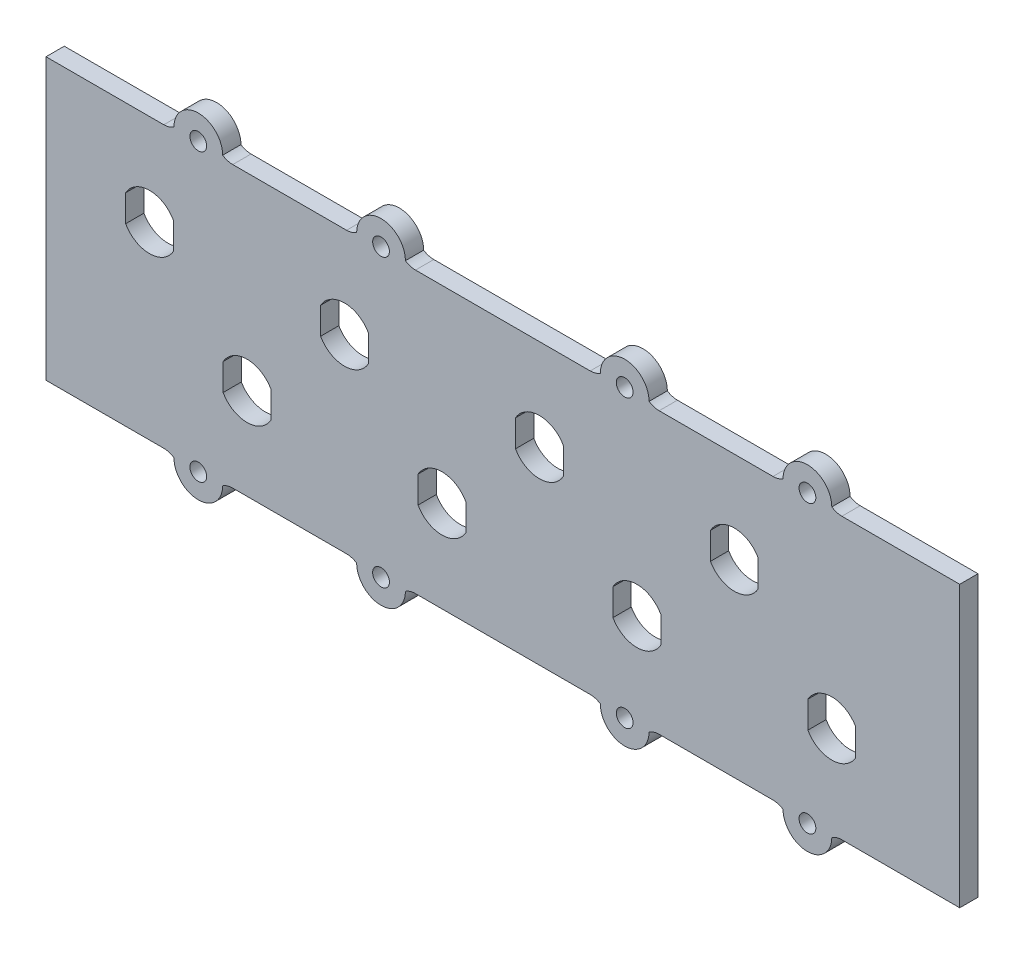
SolidWorks part; units mm, degrees
material "Aircraft Ply"
ref_plane "Front Plane" through (0, 0, 0) normal (0, 0, 1) x (1, 0, 0)
ref_plane "Top Plane" through (0, 0, 0) normal (0, 1, 0) x (1, 0, 0)
ref_plane "Right Plane" through (0, 0, 0) normal (1, 0, 0) x (0, 0, -1)
sketch "Sketch1" plane through (0, 0, 0) normal (0, 0, 1) x (1, 0, 0)
  line L0 (-75, 8) -> (75, 8) construction
  line L1 (-75, 0) -> (75, 0) construction
  line L8 (-75, 23) -> (-75, -23)
  line L9 (-44.3417, -23) -> (-25.6583, -23)
  line L10 (-14.3417, -23) -> (14.3417, -23)
  line L11 (25.6583, -23) -> (44.3417, -23)
  line L12 (75, -23) -> (75, 23)
  line L13 (44.3417, 23) -> (25.6583, 23)
  line L14 (14.3417, 23) -> (-14.3417, 23)
  line L15 (-25.6583, 23) -> (-44.3417, 23)
  line L16 (-75, 23) -> (-75, -23)
  line L17 (-44.3417, -23) -> (-25.6583, -23)
  line L18 (-14.3417, -23) -> (14.3417, -23)
  line L19 (25.6583, -23) -> (44.3417, -23)
  line L20 (75, -23) -> (75, 23)
  line L21 (44.3417, 23) -> (25.6583, 23)
  line L22 (14.3417, 23) -> (-14.3417, 23)
  line L23 (-25.6583, 23) -> (-44.3417, 23)
  line L30 (-75, -23) -> (-55.6583, -23)
  line L31 (-75, -23) -> (-55.6583, -23)
  line L32 (55.6583, -23) -> (75, -23)
  line L33 (55.6583, -23) -> (75, -23)
  line L34 (75, 23) -> (55.6583, 23)
  line L35 (75, 23) -> (55.6583, 23)
  line L36 (-55.6583, 23) -> (-75, 23)
  line L37 (-55.6583, 23) -> (-75, 23)
  line L38 (-54.075, 10.201) -> (-54.075, 5.799)
  line L39 (-61.925, 10.201) -> (-61.925, 5.799)
  line L40 (-29.925, 10.201) -> (-29.925, 5.799)
  line L41 (-22.075, 10.201) -> (-22.075, 5.799)
  line L42 (2.075, 10.201) -> (2.075, 5.799)
  line L43 (9.925, 10.201) -> (9.925, 5.799)
  line L44 (34.075, 10.201) -> (34.075, 5.799)
  line L45 (41.925, 10.201) -> (41.925, 5.799)
  line L46 (-13.925, -5.799) -> (-13.925, -10.201)
  line L47 (-6.075, -5.799) -> (-6.075, -10.201)
  line L48 (18.075, -5.799) -> (18.075, -10.201)
  line L49 (25.925, -5.799) -> (25.925, -10.201)
  line L50 (50.075, -5.799) -> (50.075, -10.201)
  line L51 (57.925, -5.799) -> (57.925, -10.201)
  line L52 (-45.925, -5.799) -> (-45.925, -10.201)
  line L53 (-38.075, -5.799) -> (-38.075, -10.201)
  circle A0 centre (-50, 23.5) radius 1.375 construction
  circle A1 centre (-20, 23.5) radius 1.375 construction
  circle A2 centre (20, 23.5) radius 1.375 construction
  circle A3 centre (50, 23.5) radius 1.375 construction
  circle A4 centre (50, -23.5) radius 1.375 construction
  circle A5 centre (20, -23.5) radius 1.375 construction
  circle A6 centre (-20, -23.5) radius 1.375 construction
  circle A7 centre (-50, -23.5) radius 1.375 construction
  circle A8 centre (-50, -23.5) radius 1.375
  circle A9 centre (-20, -23.5) radius 1.375
  circle A10 centre (20, -23.5) radius 1.375
  circle A11 centre (50, -23.5) radius 1.375
  circle A12 centre (50, 23.5) radius 1.375
  circle A13 centre (20, 23.5) radius 1.375
  circle A14 centre (-20, 23.5) radius 1.375
  circle A15 centre (-50, 23.5) radius 1.375
  circle A16 centre (-58, 8) radius 4.5
  circle A17 centre (-26, 8) radius 4.5
  circle A18 centre (6, 8) radius 4.5
  circle A19 centre (38, 8) radius 4.5
  circle A20 centre (-42, -8) radius 4.5
  circle A21 centre (-10, -8) radius 4.5
  circle A22 centre (22, -8) radius 4.5
  circle A23 centre (54, -8) radius 4.5
  arc A29 (-54, -23.5) -> (-55.6583, -23) centre (-55.6583, -26) ccw
  arc A30 (-54, -23.5) -> (-46, -23.5) centre (-50, -23.5) ccw
  arc A31 (-44.3417, -23) -> (-46, -23.5) centre (-44.3417, -26) ccw
  arc A32 (-24, -23.5) -> (-25.6583, -23) centre (-25.6583, -26) ccw
  arc A33 (-24, -23.5) -> (-16, -23.5) centre (-20, -23.5) ccw
  arc A34 (-14.3417, -23) -> (-16, -23.5) centre (-14.3417, -26) ccw
  arc A35 (16, -23.5) -> (14.3417, -23) centre (14.3417, -26) ccw
  arc A36 (16, -23.5) -> (24, -23.5) centre (20, -23.5) ccw
  arc A37 (25.6583, -23) -> (24, -23.5) centre (25.6583, -26) ccw
  arc A38 (46, -23.5) -> (44.3417, -23) centre (44.3417, -26) ccw
  arc A39 (46, -23.5) -> (54, -23.5) centre (50, -23.5) ccw
  arc A40 (55.6583, -23) -> (54, -23.5) centre (55.6583, -26) ccw
  arc A43 (54, 23.5) -> (55.6583, 23) centre (55.6583, 26) ccw
  arc A44 (54, 23.5) -> (46, 23.5) centre (50, 23.5) ccw
  arc A45 (44.3417, 23) -> (46, 23.5) centre (44.3417, 26) ccw
  arc A46 (24, 23.5) -> (25.6583, 23) centre (25.6583, 26) ccw
  arc A47 (24, 23.5) -> (16, 23.5) centre (20, 23.5) ccw
  arc A48 (14.3417, 23) -> (16, 23.5) centre (14.3417, 26) ccw
  arc A49 (-16, 23.5) -> (-14.3417, 23) centre (-14.3417, 26) ccw
  arc A50 (-16, 23.5) -> (-24, 23.5) centre (-20, 23.5) ccw
  arc A51 (-25.6583, 23) -> (-24, 23.5) centre (-25.6583, 26) ccw
  arc A52 (-46, 23.5) -> (-44.3417, 23) centre (-44.3417, 26) ccw
  arc A53 (-46, 23.5) -> (-54, 23.5) centre (-50, 23.5) ccw
  arc A54 (-55.6583, 23) -> (-54, 23.5) centre (-55.6583, 26) ccw
  arc A57 (-54, -23.5) -> (-55.6583, -23) centre (-55.6583, -26) ccw
  arc A58 (-54, -23.5) -> (-46, -23.5) centre (-50, -23.5) ccw
  arc A59 (-44.3417, -23) -> (-46, -23.5) centre (-44.3417, -26) ccw
  arc A60 (-24, -23.5) -> (-25.6583, -23) centre (-25.6583, -26) ccw
  arc A61 (-24, -23.5) -> (-16, -23.5) centre (-20, -23.5) ccw
  arc A62 (-14.3417, -23) -> (-16, -23.5) centre (-14.3417, -26) ccw
  arc A63 (16, -23.5) -> (14.3417, -23) centre (14.3417, -26) ccw
  arc A64 (16, -23.5) -> (24, -23.5) centre (20, -23.5) ccw
  arc A65 (25.6583, -23) -> (24, -23.5) centre (25.6583, -26) ccw
  arc A66 (46, -23.5) -> (44.3417, -23) centre (44.3417, -26) ccw
  arc A67 (46, -23.5) -> (54, -23.5) centre (50, -23.5) ccw
  arc A68 (55.6583, -23) -> (54, -23.5) centre (55.6583, -26) ccw
  arc A71 (54, 23.5) -> (55.6583, 23) centre (55.6583, 26) ccw
  arc A72 (54, 23.5) -> (46, 23.5) centre (50, 23.5) ccw
  arc A73 (44.3417, 23) -> (46, 23.5) centre (44.3417, 26) ccw
  arc A74 (24, 23.5) -> (25.6583, 23) centre (25.6583, 26) ccw
  arc A75 (24, 23.5) -> (16, 23.5) centre (20, 23.5) ccw
  arc A76 (14.3417, 23) -> (16, 23.5) centre (14.3417, 26) ccw
  arc A77 (-16, 23.5) -> (-14.3417, 23) centre (-14.3417, 26) ccw
  arc A78 (-16, 23.5) -> (-24, 23.5) centre (-20, 23.5) ccw
  arc A79 (-25.6583, 23) -> (-24, 23.5) centre (-25.6583, 26) ccw
  arc A80 (-46, 23.5) -> (-44.3417, 23) centre (-44.3417, 26) ccw
  arc A81 (-46, 23.5) -> (-54, 23.5) centre (-50, 23.5) ccw
  arc A82 (-55.6583, 23) -> (-54, 23.5) centre (-55.6583, 26) ccw
  dimension "D2" = 9
  dimension "D3" = 8
  dimension "D6" = 17
  dimension "D7" = 7.85
  dimension "D1" = 0
  dimension "D4" = 4
  dimension "D5" = 2
extrude "Boss-Extrude1" add sketch "Sketch1" along normal blind 3 contours A82 L37 L16 L31 A57 A58 A59 L17 A60 A61 A62 L18 A63 A64 A65 L19 A66 A67 A68 L33 L20 L35 A71 A72 A73 L21 A74 A75 A76 L22 A77 A78 A79 L23 A80 A81 A23 A22 A21 | L39 A16 | L38 A16 | L40 A17 | L41 A17 | L42 A18 | L43 A18 | L44 A19 | L45 A19 | L50 A23 | L51 A23 | L48 A22 | L49 A22 | L46 A21 | L47 A21 | L52 A20 | L53 A20 region at (0.1547, 0, 0) region at (-53.8437, 8, 0) region at (-62.1563, 8, 0) region at (-30.1563, 8, 0) region at (-21.8437, 8, 0) region at (1.8437, 8, 0) region at (10.1563, 8, 0) region at (33.8437, 8, 0) region at (42.1563, 8, 0) region at (-14.1563, -8, 0) region at (-5.8437, -8, 0) region at (17.8437, -8, 0) region at (26.1563, -8, 0) region at (49.8437, -8, 0) region at (58.1563, -8, 0) region at (-46.1563, -8, 0) region at (-37.8437, -8, 0)
sketch "Sketch2" plane through (0, 0, 3) normal (0, 0, 1) x (1, 0, 0)
  line L0 (-58, 8) -> (-42, -8) construction
  line L1 (-49.8527, 16.1473) -> (-33.8527, 0.1473)
  line L2 (-66.1473, -0.1473) -> (-50.1473, -16.1473)
  line L3 (-26, 8) -> (-10, -8) construction
  line L4 (-17.8527, 16.1473) -> (-1.8527, 0.1473)
  line L5 (-34.1473, -0.1473) -> (-18.1473, -16.1473)
  line L6 (22, -8) -> (6, 8) construction
  line L7 (13.8527, -16.1473) -> (-2.1473, -0.1473)
  line L8 (30.1473, 0.1473) -> (14.1473, 16.1473)
  line L9 (38, 8) -> (54, -8) construction
  line L10 (46.1473, 16.1473) -> (62.1473, 0.1473)
  line L11 (29.8527, -0.1473) -> (45.8527, -16.1473)
  arc A10 (-49.8527, 16.1473) -> (-66.1473, -0.1473) centre (-58, 8) ccw
  arc A11 (-50.1473, -16.1473) -> (-33.8527, 0.1473) centre (-42, -8) ccw
  arc A12 (-17.8527, 16.1473) -> (-34.1473, -0.1473) centre (-26, 8) ccw
  arc A13 (-18.1473, -16.1473) -> (-1.8527, 0.1473) centre (-10, -8) ccw
  arc A14 (13.8527, -16.1473) -> (30.1473, 0.1473) centre (22, -8) ccw
  arc A15 (14.1473, 16.1473) -> (-2.1473, -0.1473) centre (6, 8) ccw
  arc A16 (46.1473, 16.1473) -> (29.8527, -0.1473) centre (38, 8) ccw
  arc A17 (45.8527, -16.1473) -> (62.1473, 0.1473) centre (54, -8) ccw
  text T0 "      1" font "Century Gothic" height in points 18
  point P2 (-50, 0)
  point P7 (-18, 0)
  point P14 (14, 0)
  point P21 (46, 0)
sketch "Sketch3" [suppressed] plane through (0, 0, 0) normal (0, 0, 1) x (1, 0, 0)
  line L0 (75, -23) -> (75, 23) construction
  line L1 (-70, 27.5) -> (70, 27.5)
  line L2 (-75, 22.5) -> (-75, -22.5)
  line L3 (-70, -27.5) -> (70, -27.5)
  line L4 (75, 22.5) -> (75, -22.5)
  line L5 (-75, 23) -> (-75, -23) construction
  arc A0 (-46, 23.5) -> (-54, 23.5) centre (-50, 23.5) ccw construction
  arc A1 (-54, -23.5) -> (-46, -23.5) centre (-50, -23.5) ccw construction
  arc A2 (-75, -22.5) -> (-70, -27.5) centre (-70, -22.5) ccw
  arc A3 (70, -27.5) -> (75, -22.5) centre (70, -22.5) ccw
  arc A4 (70, 27.5) -> (75, 22.5) centre (70, 22.5) cw
  arc A5 (-70, 27.5) -> (-75, 22.5) centre (-70, 22.5) ccw
  circle A6 centre (-50, 23.5) radius 1.375
  circle A7 centre (50, 23.5) radius 1.375
  circle A8 centre (50, -23.5) radius 1.375
  circle A9 centre (-50, -23.5) radius 1.375
  dimension "D1" = 5
extrude "Boss-Extrude2" [suppressed] add sketch "Sketch3" along normal through all
equation "\"D6@Sketch1\"=(20+14)/2"
